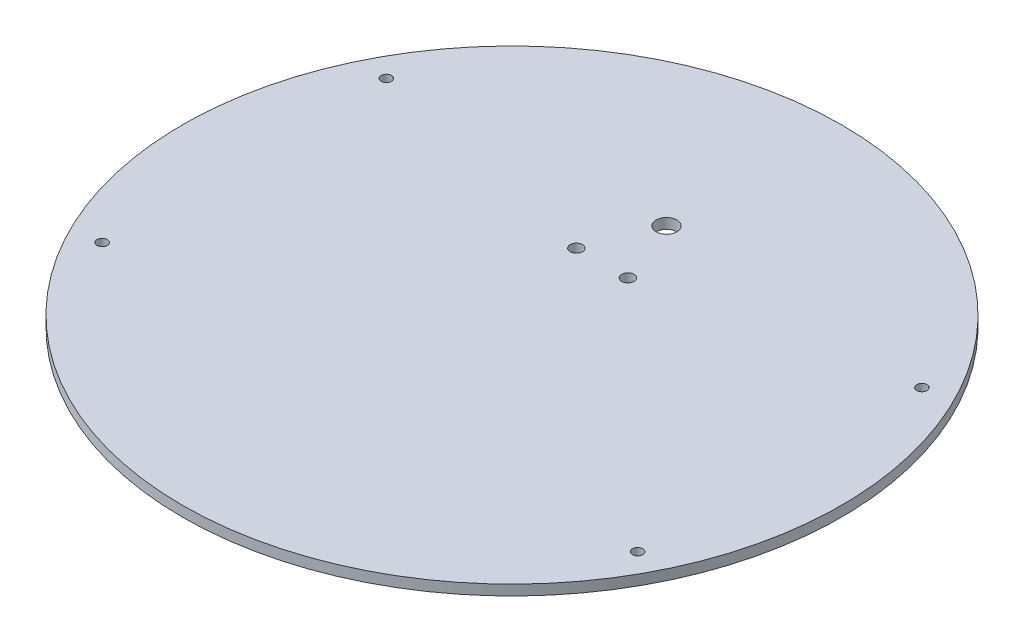
SolidWorks part; units mm, degrees
ref_plane "Front Plane" through (0, 0, 0) normal (0, 0, 1) x (1, 0, 0)
ref_plane "Top Plane" through (0, 0, 0) normal (0, 1, 0) x (1, 0, 0)
ref_plane "Right Plane" through (0, 0, 0) normal (1, 0, 0) x (0, 0, -1)
sketch "Sketch1" plane through (0, 0, 0) normal (0, 1, 0) x (1, 0, 0)
  circle A0 centre (0, 0) radius 101.6
  dimension "D1" = 203.2
extrude "Boss-Extrude1" add sketch "Sketch1" along normal blind 3.175
sketch "Sketch2" plane through (0, 3.175, 0) normal (0, 1, 0) x (1, 0, 0)
  line L0 (-82.55, 43.815) -> (-82.55, -43.815) construction
  line L1 (-82.55, -43.815) -> (82.55, -43.815) construction
  line L2 (82.55, -43.815) -> (82.55, 43.815) construction
  line L3 (82.55, 43.815) -> (-82.55, 43.815) construction
  circle A0 centre (-82.55, 43.815) radius 1.5875
  circle A1 centre (82.55, 43.815) radius 1.5875
  circle A2 centre (-82.55, -43.815) radius 1.5875
  circle A3 centre (82.55, -43.815) radius 1.5875
  dimension "D1" = 3.175
  dimension "D2" = 3.175
  dimension "D3" = 165.1
  dimension "D4" = 3.175
  dimension "D5" = 3.175
  dimension "D6" = 87.63
  dimension "D7" = 87.63
  dimension "D8" = 43.815
  dimension "D9" = 82.55
extrude "Cut-Extrude1" cut sketch "Sketch2" against normal up to next
sketch "Sketch3" plane through (0, 3.175, 0) normal (0, 1, 0) x (1, 0, 0)
  line L0 (0, 47.625) -> (0, 0) construction
  circle A0 centre (0, 47.625) radius 3.175
  dimension "D1" = 6.35
  dimension "D2" = 47.625
extrude "Cut-Extrude2" cut sketch "Sketch3" against normal up to next contours A0
ref_axis "Axis1" through (0, 3.175, 0) along (0, -1, 0)
sketch "Sketch4" plane through (0, 0, 0) normal (0, -1, 0) x (1, 0, 0)
  circle A0 centre (-7.9375, -27.7813) radius 1.905 construction
  circle A1 centre (7.9375, -27.7813) radius 1.905 construction
  circle A2 centre (-7.9375, -27.7813) radius 1.905
  circle A3 centre (7.9375, -27.7813) radius 1.905
extrude "Cut-Extrude3" cut sketch "Sketch4" against normal up to next
